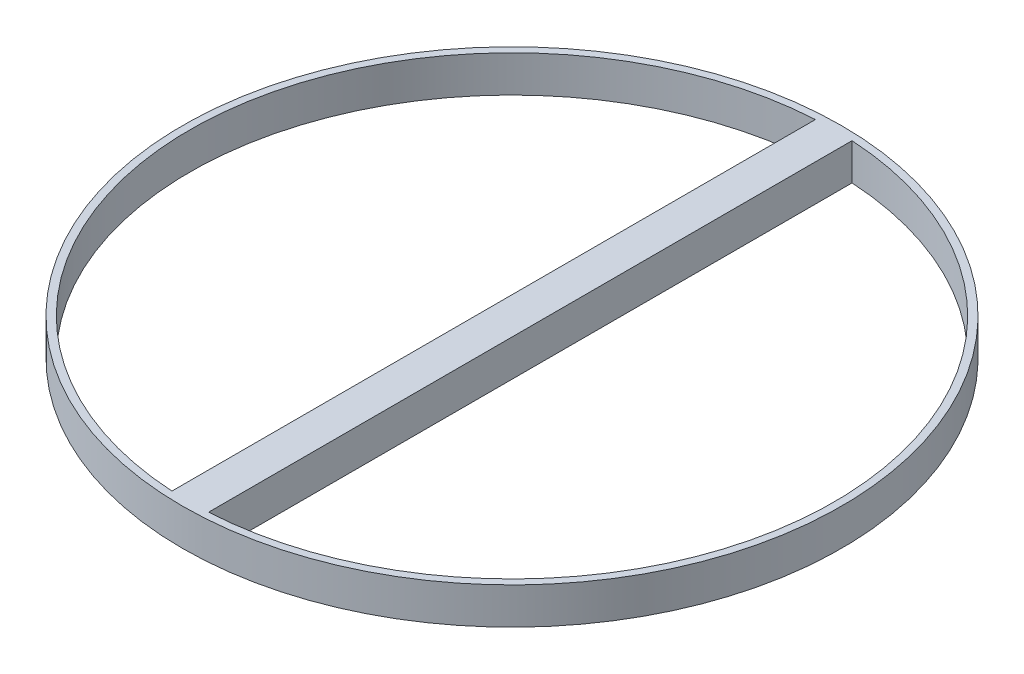
SolidWorks part; units mm, degrees
ref_plane "Front Plane" through (0, 0, 0) normal (0, 0, 1) x (1, 0, 0)
ref_plane "Top Plane" through (0, 0, 0) normal (0, 1, 0) x (1, 0, 0)
ref_plane "Right Plane" through (0, 0, 0) normal (1, 0, 0) x (0, 0, -1)
sketch "Sketch1" plane through (0, 0, 0) normal (0, 1, 0) x (1, 0, 0)
  line L2 (-5, 87.8578) -> (-5, -87.8578)
  line L3 (5, 87.8578) -> (5, -87.8578)
  circle A0 centre (0, 0) radius 90
  arc A1 (5, -87.8578) -> (5, 87.8578) centre (0, 0) ccw
  circle A2 centre (0, 0) radius 88 construction
  arc A3 (-5, 87.8578) -> (-5, -87.8578) centre (0, 0) ccw
  dimension "D1" = 180
  dimension "D2" = 2
extrude "Boss-Extrude2" add sketch "Sketch1" along normal blind 10
